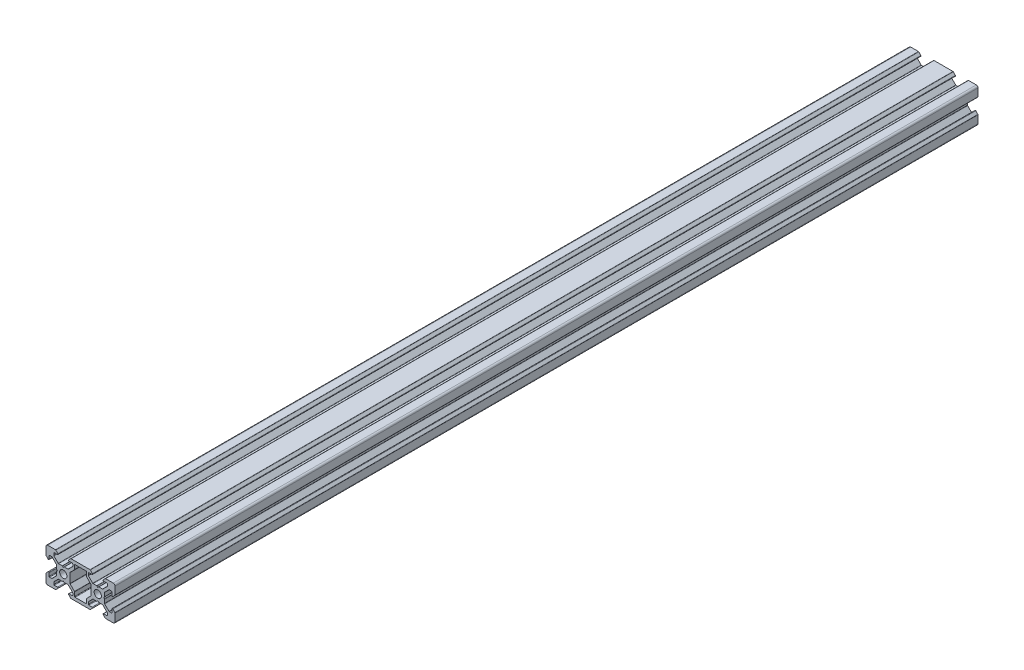
SolidWorks part; units mm, degrees
material "АД31Т ГОСТ 4784-97"
ref_plane "Спереди" through (0, 0, 0) normal (0, 0, 1) x (1, 0, 0)
ref_plane "Сверху" through (0, 0, 0) normal (0, 1, 0) x (1, 0, 0)
ref_plane "Справа" through (0, 0, 0) normal (1, 0, 0) x (0, 0, -1)
sketch "Эскиз1" plane through (0, 0, 0) normal (0, 0, 1) x (1, 0, 0)
  line L0 (12.9654, 0) -> (-12.9654, 0) construction
  line L1 (0, -12.9654) -> (0, 12.9654) construction
  line L2 (0, 0) -> (-18.3359, -18.3359) construction
  line L3 (-10, -10) -> (-10, -4.4)
  line L4 (-10, -4.4) -> (-8.2, -2.6)
  line L5 (-8.2, -2.6) -> (-8.2, -5.4993)
  line L6 (-8.2, -5.4993) -> (-6.56, -5.4993)
  line L7 (-6.56, -5.4993) -> (-3.9007, -2.84)
  line L8 (-3.9007, -2.84) -> (-3.9007, -0.5)
  line L9 (-3.9007, -0.5) -> (-3.4007, 0)
  line L10 (-0.5, -3.9007) -> (0, -3.4007)
  line L11 (-2.84, -3.9007) -> (-0.5, -3.9007)
  line L12 (-5.4993, -6.56) -> (-2.84, -3.9007)
  line L13 (-5.4993, -8.2) -> (-5.4993, -6.56)
  line L14 (-2.6, -8.2) -> (-5.4993, -8.2)
  line L15 (-4.4, -10) -> (-2.6, -8.2)
  line L16 (-10, -10) -> (-4.4, -10)
  line L17 (-10, 10) -> (-4.4, 10)
  line L18 (-4.4, 10) -> (-2.6, 8.2)
  line L19 (-2.6, 8.2) -> (-5.4993, 8.2)
  line L20 (-5.4993, 8.2) -> (-5.4993, 6.56)
  line L21 (-5.4993, 6.56) -> (-2.84, 3.9007)
  line L22 (-2.84, 3.9007) -> (-0.5, 3.9007)
  line L23 (-0.5, 3.9007) -> (0, 3.4007)
  line L24 (-3.9007, 0.5) -> (-3.4007, 0)
  line L25 (-3.9007, 2.84) -> (-3.9007, 0.5)
  line L26 (-6.56, 5.4993) -> (-3.9007, 2.84)
  line L27 (-8.2, 5.4993) -> (-6.56, 5.4993)
  line L28 (-8.2, 2.6) -> (-8.2, 5.4993)
  line L29 (-10, 4.4) -> (-8.2, 2.6)
  line L30 (-10, 10) -> (-10, 4.4)
  line L31 (0.5, 3.9007) -> (0, 3.4007)
  line L32 (0.5, -3.9007) -> (0, -3.4007)
  line L33 (10, -10) -> (10, 10) construction
  line L34 (3.9007, -0.5) -> (3.9007, 0.5)
  line L35 (6.56, -5.4993) -> (6.56, -8.2)
  line L36 (13.44, -5.4993) -> (16.0993, -2.84)
  line L37 (6.56, 5.4993) -> (3.9007, 2.84)
  line L38 (3.9007, 2.84) -> (3.9007, 0.5)
  line L39 (6.56, -8.2) -> (13.44, -8.2)
  line L40 (2.84, 3.9007) -> (0.5, 3.9007)
  line L41 (5.4993, 6.56) -> (2.84, 3.9007)
  line L42 (5.4993, 8.2) -> (5.4993, 6.56)
  line L43 (2.6, 8.2) -> (5.4993, 8.2)
  line L44 (4.4, 10) -> (2.6, 8.2)
  line L45 (15.6, 10) -> (4.4, 10)
  line L46 (15.6, -10) -> (4.4, -10)
  line L47 (4.4, -10) -> (2.6, -8.2)
  line L48 (2.6, -8.2) -> (5.4993, -8.2)
  line L49 (5.4993, -8.2) -> (5.4993, -6.56)
  line L50 (5.4993, -6.56) -> (2.84, -3.9007)
  line L51 (2.84, -3.9007) -> (0.5, -3.9007)
  line L52 (6.56, 5.4993) -> (6.56, 8.2)
  line L53 (3.9007, -2.84) -> (3.9007, -0.5)
  line L54 (6.56, -5.4993) -> (3.9007, -2.84)
  line L55 (16.0993, -2.84) -> (16.0993, -0.5)
  line L56 (6.56, 8.2) -> (13.44, 8.2)
  line L57 (13.44, 5.4993) -> (13.44, 8.2)
  line L58 (17.16, -3.9007) -> (19.5, -3.9007)
  line L59 (14.5007, -6.56) -> (17.16, -3.9007)
  line L60 (14.5007, -8.2) -> (14.5007, -6.56)
  line L61 (17.4, -8.2) -> (14.5007, -8.2)
  line L62 (15.6, -10) -> (17.4, -8.2)
  line L63 (15.6, 10) -> (17.4, 8.2)
  line L64 (17.4, 8.2) -> (14.5007, 8.2)
  line L65 (14.5007, 8.2) -> (14.5007, 6.56)
  line L66 (14.5007, 6.56) -> (17.16, 3.9007)
  line L67 (17.16, 3.9007) -> (19.5, 3.9007)
  line L68 (16.0993, 2.84) -> (16.0993, 0.5)
  line L69 (13.44, 5.4993) -> (16.0993, 2.84)
  line L70 (13.44, -5.4993) -> (13.44, -8.2)
  line L71 (16.0993, -0.5) -> (16.0993, 0.5)
  line L72 (19.5, -3.9007) -> (20, -3.4007)
  line L73 (19.5, 3.9007) -> (20, 3.4007)
  line L74 (30, 10) -> (30, 4.4)
  line L75 (30, 4.4) -> (28.2, 2.6)
  line L76 (28.2, 2.6) -> (28.2, 5.4993)
  line L77 (28.2, 5.4993) -> (26.56, 5.4993)
  line L78 (26.56, 5.4993) -> (23.9007, 2.84)
  line L79 (23.9007, 2.84) -> (23.9007, 0.5)
  line L80 (23.9007, 0.5) -> (23.4007, 0)
  line L81 (20.5, 3.9007) -> (20, 3.4007)
  line L82 (22.84, 3.9007) -> (20.5, 3.9007)
  line L83 (25.4993, 6.56) -> (22.84, 3.9007)
  line L84 (25.4993, 8.2) -> (25.4993, 6.56)
  line L85 (22.6, 8.2) -> (25.4993, 8.2)
  line L86 (24.4, 10) -> (22.6, 8.2)
  line L87 (30, 10) -> (24.4, 10)
  line L88 (30, -10) -> (24.4, -10)
  line L89 (24.4, -10) -> (22.6, -8.2)
  line L90 (22.6, -8.2) -> (25.4993, -8.2)
  line L91 (25.4993, -8.2) -> (25.4993, -6.56)
  line L92 (25.4993, -6.56) -> (22.84, -3.9007)
  line L93 (22.84, -3.9007) -> (20.5, -3.9007)
  line L94 (20.5, -3.9007) -> (20, -3.4007)
  line L95 (23.9007, -0.5) -> (23.4007, 0)
  line L96 (23.9007, -2.84) -> (23.9007, -0.5)
  line L97 (26.56, -5.4993) -> (23.9007, -2.84)
  line L98 (28.2, -5.4993) -> (26.56, -5.4993)
  line L99 (28.2, -2.6) -> (28.2, -5.4993)
  line L100 (30, -4.4) -> (28.2, -2.6)
  line L101 (30, -10) -> (30, -4.4)
  circle A0 centre (0, 0) radius 2.1
  circle A1 centre (20, 0) radius 2.1
  point P62 (10, 8.2)
  point P80 (10, -8.2)
  dimension "D5" = 2.6
  dimension "D10" = 4.2
  dimension "D2" = 10
  dimension "D3" = 1.64
  dimension "D4" = 1.5
  dimension "D6" = 1.8
  dimension "D7" = 2.84
  dimension "D8" = 0.5
  dimension "D9" = 45
extrude "Бобышка-Вытянуть1" add sketch "Эскиз1" along normal up to surface (500 mm away)
fillet "Скругление1" radius 1 4 edges at (-10, 10, 250) (-10, -10, 250) (30, 10, 250) (30, -10, 250)
fillet "Скругление2" radius 0.3 83 edges at (-4.4, 10, 250) (-2.6, 8.2, 250) (-5.4993, 8.2, 250) (-5.4993, 6.56, 250) (-2.84, 3.9007, 250) (-0.5, 3.9007, 250) (0.5, 3.9007, 250) (2.84, 3.9007, 250) (5.4993, 6.56, 250) (4.4, 10, 250) (5.4993, 8.2, 250) (2.6, 8.2, 250) (3.9007, 2.84, 250) (3.9007, -2.84, 250) (4.4, -10, 250) (2.6, -8.2, 250) (5.4993, -8.2, 250) (5.4993, -6.56, 250) (2.84, -3.9007, 250) (0.5, -3.9007, 250) (-0.5, -3.9007, 250) (-2.84, -3.9007, 250) (-5.4993, -6.56, 250) (-5.4993, -8.2, 250) (-2.6, -8.2, 250) (-10, -4.4, 250) (-8.2, -2.6, 250) (-8.2, -5.4993, 250) (-6.56, -5.4993, 250) (-3.9007, -2.84, 250) (-3.9007, -0.5, 250) (-3.9007, 0.5, 250) (-3.9007, 2.84, 250) (-6.56, 5.4993, 250) (-8.2, 5.4993, 250) (-8.2, 2.6, 250) (-10, 4.4, 250) (6.56, -5.4993, 250) (6.56, 5.4993, 250) (6.56, 8.2, 250) (13.44, 8.2, 250) (13.44, 5.4993, 250) (16.0993, 2.84, 250) (16.0993, -2.84, 250) (13.44, -5.4993, 250) (13.44, -8.2, 250) (6.56, -8.2, 250) (15.6, 10, 250) (17.4, 8.2, 250) (14.5007, 8.2, 250) (14.5007, 6.56, 250) (17.16, 3.9007, 250) (19.5, 3.9007, 250) (20.5, 3.9007, 250) (22.84, 3.9007, 250) (25.4993, 6.56, 250) (25.4993, 8.2, 250) (22.6, 8.2, 250) (24.4, 10, 250) (30, 4.4, 250) (28.2, 2.6, 250) (28.2, 5.4993, 250) (26.56, 5.4993, 250) (23.9007, 2.84, 250) (23.9007, 0.5, 250) (23.9007, -0.5, 250) (23.9007, -2.84, 250) (26.56, -5.4993, 250) (28.2, -5.4993, 250) (28.2, -2.6, 250) (30, -4.4, 250) (24.4, -10, 250) (22.6, -8.2, 250) (25.4993, -8.2, 250) (25.4993, -6.56, 250) (22.84, -3.9007, 250) (20.5, -3.9007, 250) (19.5, -3.9007, 250) (17.16, -3.9007, 250) (14.5007, -6.56, 250) (14.5007, -8.2, 250) (17.4, -8.2, 250) (15.6, -10, 250)
